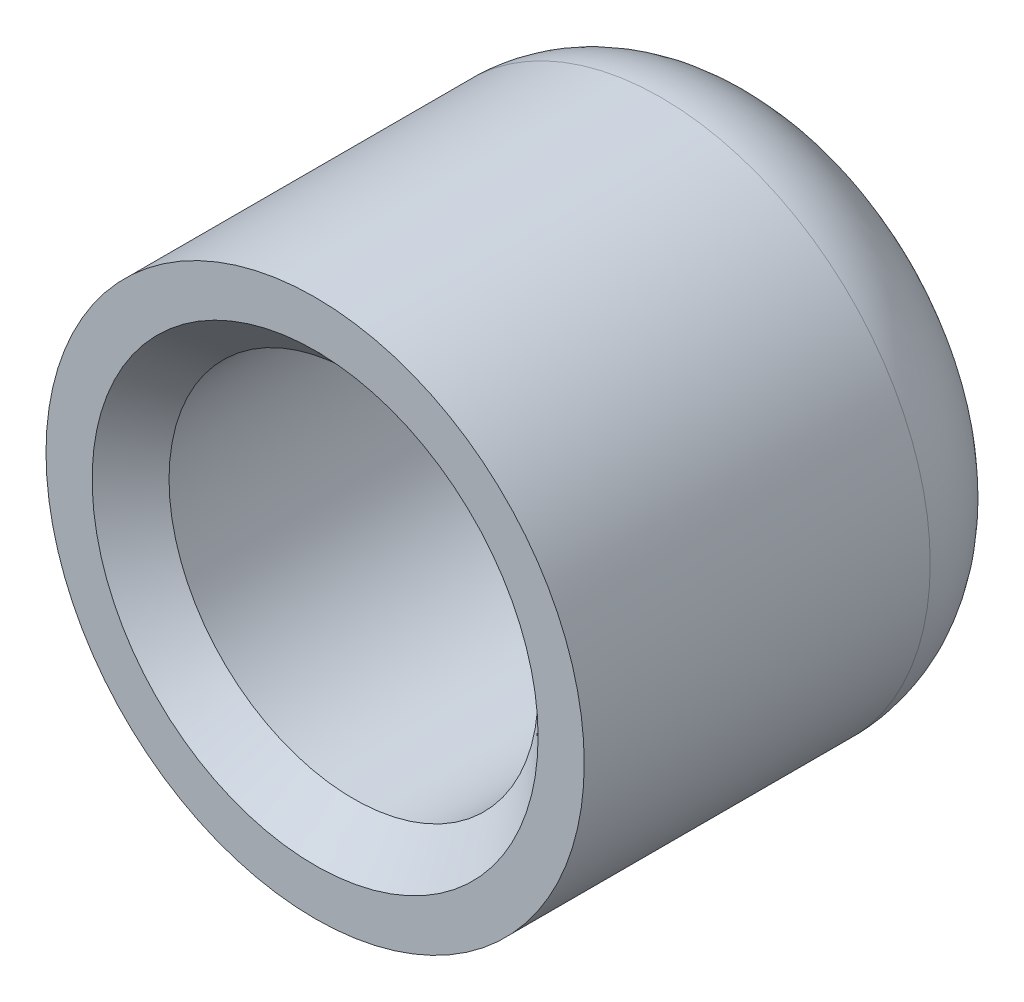
SolidWorks part; units mm, degrees
ref_plane "Front Plane" through (0, 0, 0) normal (0, 0, 1) x (1, 0, 0)
ref_plane "Top Plane" through (0, 0, 0) normal (0, 1, 0) x (1, 0, 0)
ref_plane "Right Plane" through (0, 0, 0) normal (1, 0, 0) x (0, 0, -1)
sketch "Sketch1" plane through (0, 0, 0) normal (0, 0, 1) x (1, 0, 0)
  circle A0 centre (0, 0) radius 2.4
  circle A1 centre (0, 0) radius 3.5
  dimension "D1" = 4.8
  dimension "D2" = 1.1
extrude "Boss-Extrude1" add sketch "Sketch1" along normal blind 6
extrude "Boss-Extrude2" add sketch "Sketch1<2>" along normal blind 1 contours A0 region at (0, 0, 0)
sketch "Sketch1<2>" plane through (0, 0, 0) normal (0, 0, 1) x (1, 0, 0) same geometry as "Sketch1"
fillet "Fillet1" radius 1.5 1 edges at (3.5, 0, 0)
chamfer "Chamfer1" distance 0.5 angle 45 1 edges at (2.4, 0, 6)
